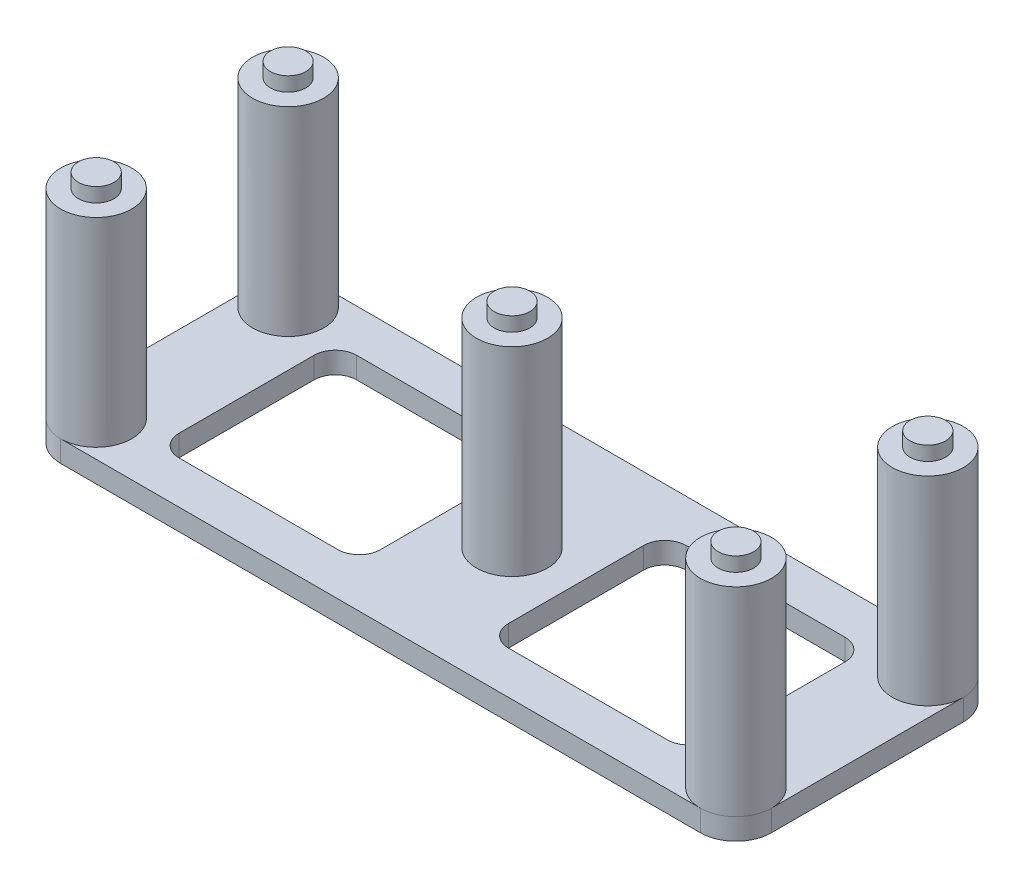
SolidWorks part; units mm, degrees
ref_plane "Front Plane" through (0, 0, 0) normal (0, 0, 1) x (1, 0, 0)
ref_plane "Top Plane" through (0, 0, 0) normal (0, 1, 0) x (1, 0, 0)
ref_plane "Right Plane" through (0, 0, 0) normal (1, 0, 0) x (0, 0, -1)
sketch "Sketch1" plane through (0, 0, 0) normal (0, 1, 0) x (1, 0, 0)
  line L1 (-50, -18.5) -> (50, -18.5)
  line L2 (-50, -18.5) -> (-50, 18.5)
  line L3 (-50, 18.5) -> (50, 18.5)
  line L4 (50, -18.5) -> (50, 18.5)
  line L5 (-50, -18.5) -> (50, 18.5) construction
  line L6 (-50, 18.5) -> (50, -18.5) construction
  point P0 (0, 0)
  dimension "D1" = 37
  dimension "D2" = 100
extrude "Boss-Extrude1" add sketch "Sketch1" along normal mid plane 3
sketch "Sketch2" plane through (0, 1.5, 0) normal (0, 1, 0) x (1, 0, 0)
  line L1 (50, 18.5) -> (-50, 18.5) construction
  line L2 (-45, 13.5) -> (45, 13.5) construction
  line L3 (-45, 13.5) -> (-45, -13.5) construction
  line L4 (-45, -13.5) -> (45, -13.5) construction
  line L5 (45, 13.5) -> (45, -13.5) construction
  line L6 (-50, 18.5) -> (-50, -18.5) construction
  line L7 (-45, 13.5) -> (45, -13.5) construction
  line L8 (-45, -13.5) -> (45, 13.5) construction
  circle A0 centre (-45, 13.5) radius 5
  circle A1 centre (45, 13.5) radius 5
  circle A2 centre (45, -13.5) radius 5
  circle A3 centre (-45, -13.5) radius 5
  circle A4 centre (0, 0) radius 5
  point P12 (0, 13.5)
  point P13 (-45, 0)
  dimension "D1" = 10
  dimension "D2" = 5
  dimension "D3" = 5
extrude "Boss-Extrude2" add sketch "Sketch2" along normal blind 28
sketch "Sketch3" plane through (0, 29.5, 0) normal (0, 1, 0) x (1, 0, 0)
  circle A0 centre (-45, 13.5) radius 2.5
  circle A1 centre (45, 13.5) radius 2.5
  circle A2 centre (45, -13.5) radius 2.5
  circle A3 centre (-45, -13.5) radius 2.5
  circle A4 centre (0, 0) radius 2.5
  dimension "D1" = 5
extrude "Boss-Extrude3" add sketch "Sketch3" along normal blind 2
sketch "Sketch4" plane through (0, 1.5, 0) normal (0, 1, 0) x (1, 0, 0)
  line L0 (-45, 13.5) -> (-45, -13.5) construction
  line L1 (-37.3581, 12.5) -> (-9, 12.5)
  line L2 (-37.3581, 12.5) -> (-37.3581, -12.5)
  line L3 (-37.3581, -12.5) -> (-9, -12.5)
  line L4 (-9, 12.5) -> (-9, -12.5)
  line L5 (9, 12.5) -> (37.3581, 12.5)
  line L6 (9, 12.5) -> (9, -12.5)
  line L7 (9, -12.5) -> (37.3581, -12.5)
  line L8 (37.3581, 12.5) -> (37.3581, -12.5)
  line L9 (0, 0) -> (-45, 0) construction
  line L10 (-9, 12.5) -> (9, 12.5) construction
  point P15 (-37.3581, 0)
  point P16 (0, 12.5)
  dimension "D1" = 25
  dimension "D2" = 18
  dimension "D3" = 28.3581
extrude "Cut-Extrude1" cut sketch "Sketch4" against normal up to next
fillet "Fillet1" radius 3 8 edges at (37.3581, 0, 12.5) (37.3581, 0, -12.5) (9, 0, -12.5) (9, 0, 12.5) (-37.3581, 0, 12.5) (-9, 0, 12.5) (-9, 0, -12.5) (-37.3581, 0, -12.5)
sketch "Sketch5" plane through (0, 31.5, 0) normal (0, 1, 0) x (1, 0, 0)
  line L0 (50, -13.5) -> (50, 13.5) construction
  line L1 (-50, 18.5) -> (50, 18.5)
  line L2 (-50, 18.5) -> (-50, -8.5)
  line L4 (50, 18.5) -> (50, -18.5)
  line L5 (-45, -18.5) -> (45, -18.5) construction
  line L6 (50, -18.5) -> (-40, -18.5)
  line L7 (-40, -18.5) -> (-40, -8.5)
  line L8 (-40, -8.5) -> (-50, -8.5)
  circle A0 centre (-45, -13.5) radius 5 construction
extrude "Cut-Extrude2" [suppressed] cut sketch "Sketch5" against normal up to next
fillet "Fillet4" radius 5 4 edges at (50, 0, 18.5) (-50, 0, -18.5) (-50, 0, 18.5) (50, 0, -18.5)
